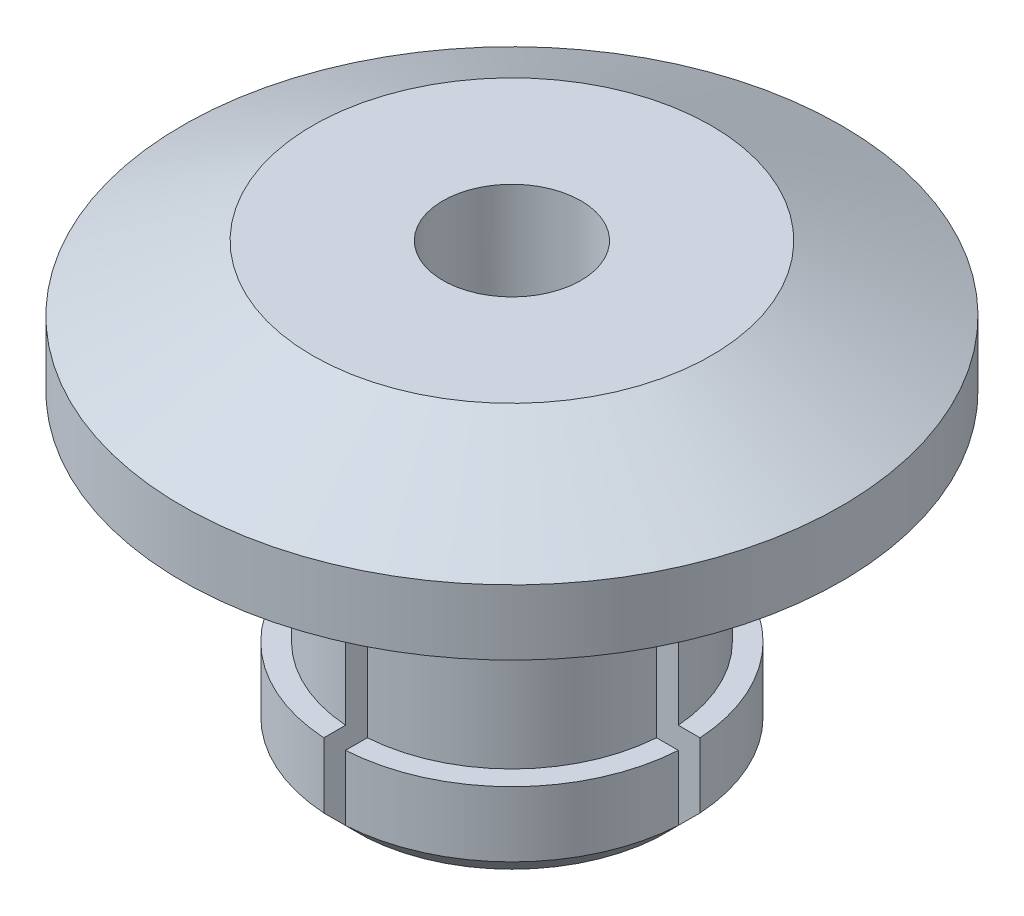
SolidWorks part; units mm, degrees
other "Marquage1"
sketch "Esquisse5" plane through (7.59, -10.8708, 7.59) normal (0.8599, -0.5049, 0.0753) x (0.5079, 0.8312, -0.2262)
ref_plane "Plan de face" through (0, 0, 0) normal (0, 0, 1) x (1, 0, 0)
ref_plane "Plan de dessus" through (0, 0, 0) normal (0, 1, 0) x (1, 0, 0)
ref_plane "Plan de droite" through (0, 0, 0) normal (1, 0, 0) x (0, 0, -1)
sketch "Esquisse1" plane through (0, 0, 0) normal (0, 0, 1) x (1, 0, 0)
  line L0 (1.59, -0.8708) -> (4.59, -0.8708)
  line L1 (4.59, -0.8708) -> (7.59, -2.3708)
  line L2 (7.59, -2.3708) -> (7.59, -3.8708)
  line L3 (7.59, -3.8708) -> (3.59, -3.8708)
  line L4 (3.59, -3.8708) -> (3.59, -8.8708)
  line L26 (0, 0) -> (0, 15.0012) construction
  line L29 (3.59, -8.8708) -> (4.09, -8.8708)
  line L30 (4.09, -8.8708) -> (4.09, -10.3708)
  line L31 (4.09, -10.3708) -> (3.59, -10.8708)
  line L32 (3.59, -10.8708) -> (1.59, -10.8708)
  line L40 (1.59, -0.8708) -> (1.59, -7.8708)
  line L41 (1.59, -10.8708) -> (1.09, -10.3708)
  line L42 (1.09, -10.3708) -> (1.59, -9.8708)
  line L43 (1.59, -9.8708) -> (1.09, -9.3708)
  line L44 (1.09, -9.3708) -> (1.59, -8.8708)
  line L45 (1.59, -8.8708) -> (1.09, -8.3708)
  line L46 (1.09, -8.3708) -> (1.59, -7.8708)
  point P0 (0, 0)
  dimension "D2" = 3
  dimension "D3" = 1.5
  dimension "D4" = 1.59
  dimension "D5" = 0.5
  dimension "D6" = 2
  dimension "D7" = 0
  dimension "D8" = 1.5
  dimension "D9" = 0.5
  dimension "D10" = 0.5
  dimension "D11" = 3
  dimension "D12" = 3
  dimension "D13" = 0.5
  dimension "D14" = 0.5
ref_axis "Axe1" through (0, 19.4425, 0) along (0, -1, 0)
revolve "Révolution1" add sketch "Esquisse1" angle 360 about L26
sketch "Esquisse4" plane through (0, -10.8708, 0) normal (0, -1, 0) x (1, 0, 0)
  line L0 (-0.25, 0.25) -> (-6.9389, 0.25)
  line L1 (-0.25, 5.8583) -> (0.25, 5.8583)
  line L2 (-0.25, 5.8583) -> (-0.25, 0.25)
  line L3 (-0.25, -5.5852) -> (0.25, -5.5852)
  line L4 (0.25, 5.8583) -> (0.25, 0.25)
  line L5 (11.3525, -0.25) -> (0.25, -0.25)
  line L6 (11.3525, -0.25) -> (11.3525, 0.25)
  line L7 (11.3525, 0.25) -> (0.25, 0.25)
  line L8 (-6.9389, -0.25) -> (-6.9389, 0.25)
  line L9 (-0.25, -0.25) -> (-6.9389, -0.25)
  line L10 (-0.25, -0.25) -> (-0.25, -5.5852)
  line L11 (0.25, -0.25) -> (0.25, -5.5852)
  dimension "D1" = 0.5
  dimension "D2" = 0.5
  dimension "D3" = 0.25
  dimension "D4" = 0.25
extrude "Enlèv. mat.-Extru.2" cut sketch "Esquisse4" against normal up to surface (7 mm away) up to face at (0, -3.8708, -7.59)
